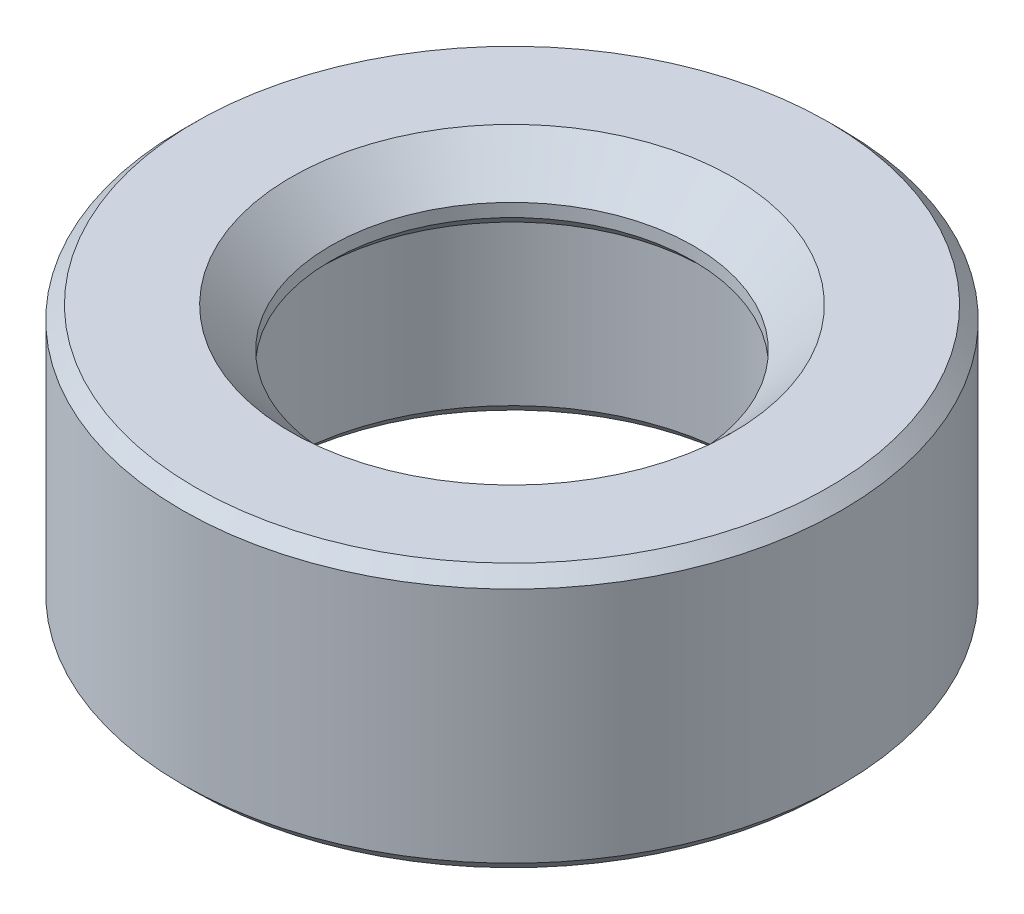
SolidWorks part; units mm, degrees
ref_plane "Ebene vorne" through (0, 0, 0) normal (0, 0, 1) x (1, 0, 0)
ref_plane "Ebene oben" through (0, 0, 0) normal (0, 1, 0) x (1, 0, 0)
ref_plane "Ebene rechts" through (0, 0, 0) normal (1, 0, 0) x (0, 0, -1)
sketch "Skizze1" plane through (0, 0, 0) normal (1, 0, 0) x (0, 0, -1)
  line L0 (0, 14.193) -> (0, -13.0854) construction
  line L1 (-15.1899, 0) -> (14.6519, 0) construction
  line L2 (3.5, -2) -> (3.5, 1)
  line L3 (3.5, 1) -> (2.75, 1)
  line L4 (2.75, 1) -> (2.75, 2)
  line L5 (2.75, 2) -> (5, 2)
  line L6 (5, 2) -> (5, -2)
  line L7 (5, -2) -> (3.5, -2)
  dimension "D1" = 10
  dimension "D2" = 7
  dimension "D3" = 3
  dimension "D4" = 4
  dimension "D5" = 5.5
revolve "Rotation1" add sketch "Skizze1" angle 360 about L0
ref_axis "Achse1" through (0, -14.4494, 0) along (0, 1, 0)
chamfer "Fase1" distance 0.2 angle 45 4 edges at (0, 1, 2.75) (0, -2, 3.5) (0, -2, 5) (0, 2, 5)
chamfer "Fase2" distance 0.6 angle 45 1 edges at (0, 2, 2.75)
